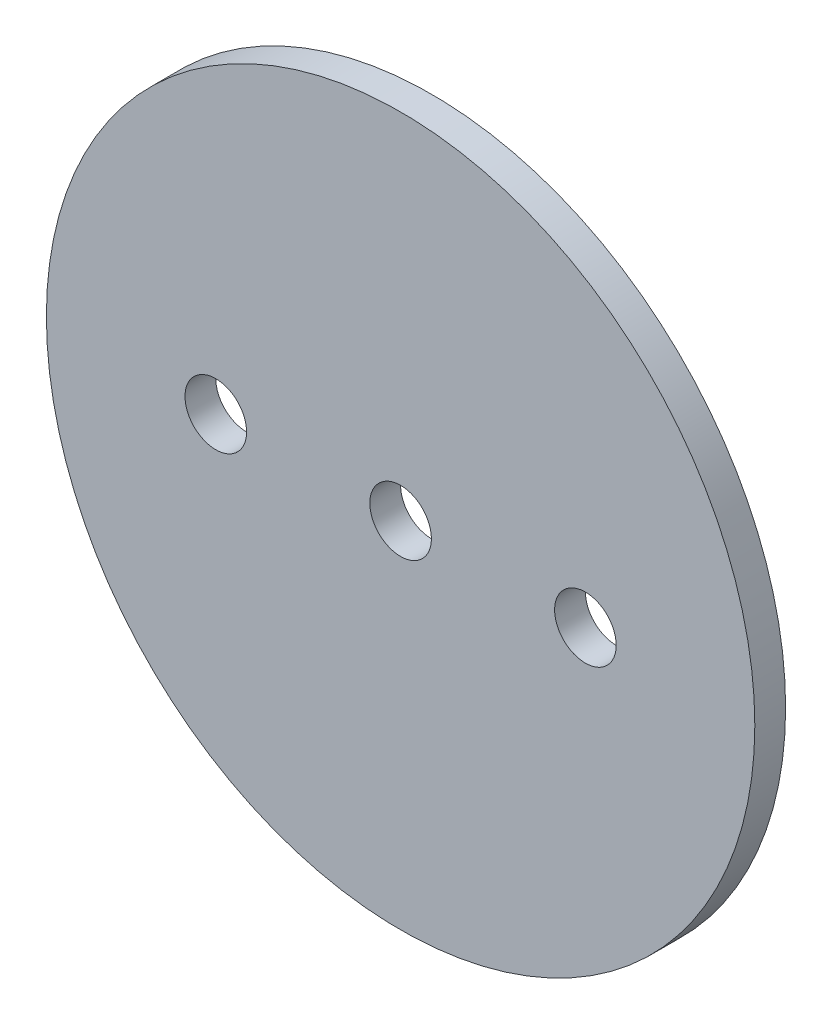
SolidWorks part; units mm, degrees
ref_plane "Front Plane" through (0, 0, 0) normal (0, 0, 1) x (1, 0, 0)
ref_plane "Top Plane" through (0, 0, 0) normal (0, 1, 0) x (1, 0, 0)
ref_plane "Right Plane" through (0, 0, 0) normal (1, 0, 0) x (0, 0, -1)
sketch "Sketch1" plane through (0, 0, 0) normal (0, 0, 1) x (1, 0, 0)
  circle A0 centre (0, 0) radius 36.5125
  dimension "D1" = 73.025
extrude "Boss-Extrude1" add sketch "Sketch1" along normal mid plane 3.175
sketch "Sketch2" plane through (0, 0, 1.5875) normal (0, 0, 1) x (1, 0, 0)
  line L0 (-1000, 0) -> (49000, 0) construction
  point P1 (0, 0)
  point P4 (19.05, 0)
  point P5 (-19.05, 0)
  dimension "D1" = 19.05
  dimension "D2" = 38.1
hole_wizard "1/4 (0.25) Diameter Hole1" positions "Sketch2" profile "Sketch3" hole size "1/4" standard "ANSI Inch" end condition through all
sketch "Sketch3" plane through (-19.05, 0, 1.5875) normal (1, 0, 0) x (0, -1, 0)
  line L0 (0, 0) -> (0, 3.175)
  line L1 (0, 3.175) -> (3.175, 3.175)
  line L2 (3.175, 3.175) -> (3.175, 0)
  line L5 (3.175, 0) -> (0, 0)
  line L11 (0, -6.35) -> (0, 107.95) construction
  dimension "Thru Hole Dia." = 6.35
  dimension "Thru Hole Depth" = 3.175
equation "\"AIRFRAME_OD\"= 3.091in"
equation "\"AIRFRAME_ID\"= 3.00in"
equation "\"FLAT_T\"= 0.125in"
equation "\"NOSE_EXP_L\"= 3.5in"
equation "\"NOSE_SHOULDER_L\"= 5in"
equation "\"MAIN_L\"= 30in"
equation "\"RECO_COUP_L\"= 6in"
equation "\"RECO_SWITCH_L\"= 1.5in"
equation "\"DROGUE_L\"= 14in"
equation "\"ATS_FORE_COUP_L\"= 4in"
equation "\"ATS_AFT_COUP_L\"= 4in"
equation "\"LOWER_L\"= 16in"
equation "\"FIN_N\"= 4"
equation "\"CR_AFT_X\"= 0.5in"
equation "\"CR_FORE_X\"= 6in"
equation "\"FIN_ROOT\"= 5in"
equation "\"FIN_X\"= 0.75in"
equation "\"MOTOR_OD\"= 2.25in"
equation "\"MOTOR_ID\"= 2.126in"
equation "\"COUPLER_OD\"= 2.998in"
equation "\"COUPLER_ID\"= 2.875in"
equation "\"D1@Sketch1\"=\"COUPLER_ID\""
equation "\"D1@Boss-Extrude1\"=\"FLAT_T\""
equation "\"RECO_ROD_X\"= 1.5in"
equation "\"ATS_ROD_X\"= 2in"
equation "\"D1@Sketch2\"=\"RECO_ROD_X\"*0.5"
equation "\"D2@Sketch2\"=\"RECO_ROD_X\""
